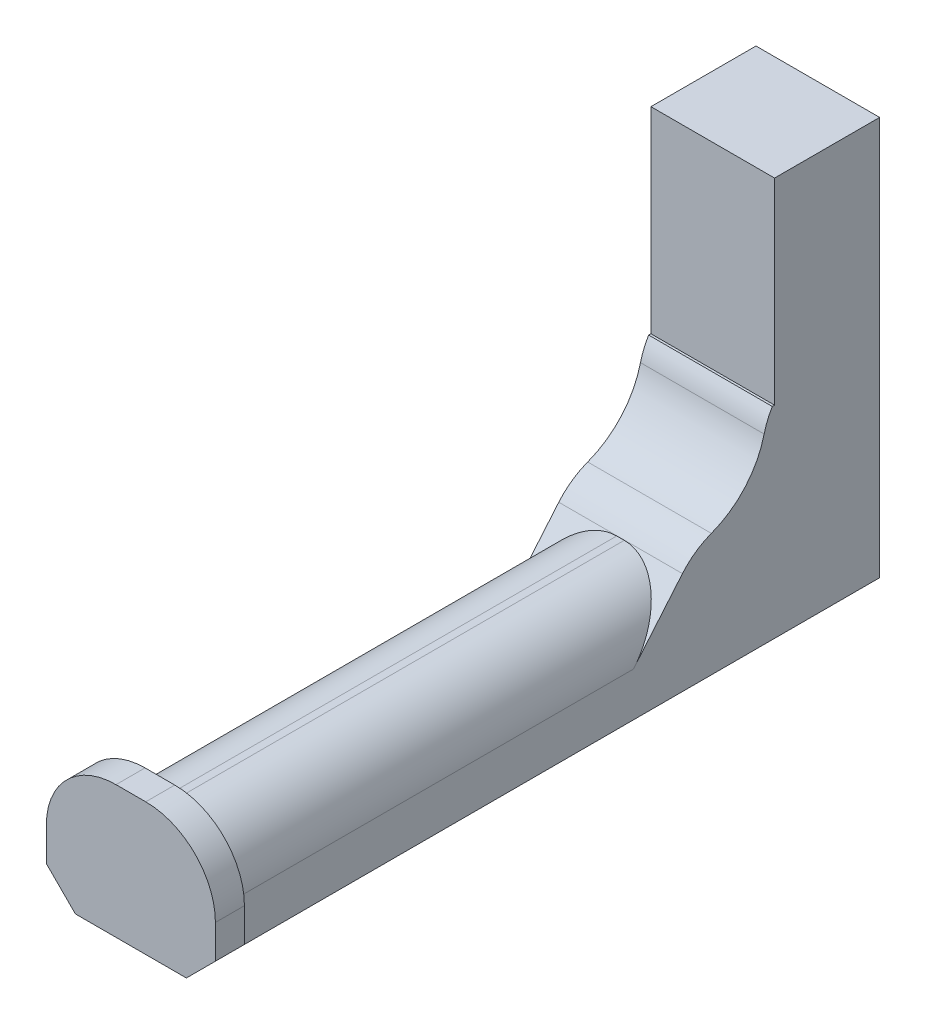
SolidWorks part; units mm, degrees
ref_plane "Front" through (0, 0, 0) normal (0, 0, 1) x (1, 0, 0)
ref_plane "Top" through (0, 0, 0) normal (0, 1, 0) x (1, 0, 0)
ref_plane "Right" through (0, 0, 0) normal (1, 0, 0) x (0, 0, -1)
sketch "Sketch1" plane through (0, 0, 0) normal (0, 0, 1) x (1, 0, 0)
  line L1 (-10.65, -35) -> (10.65, -35)
  line L2 (-10.65, -35) -> (-10.65, 35)
  line L3 (-10.65, 35) -> (10.65, 35)
  line L4 (10.65, -35) -> (10.65, 35)
  line L5 (-10.65, -35) -> (10.65, 35) construction
  line L6 (-10.65, 35) -> (10.65, -35) construction
  point P0 (0, 0)
extrude "Boss-Extrude1" add sketch "Sketch1" against normal blind 3
sketch "Sketch2" plane through (0, 0, -3) normal (0, 0, -1) x (-1, 0, 0)
  line L0 (10.65, -35) -> (-10.65, -35) construction
  line L1 (-10.65, 35) -> (-7.7, 35)
  line L2 (-10.65, 35) -> (-10.65, -35)
  line L3 (-10.65, -35) -> (-7.7, -35)
  line L4 (-7.7, 35) -> (-7.7, -35)
  line L6 (10.65, 35) -> (7.7, 35)
  line L7 (10.65, 35) -> (10.65, -35)
  line L8 (10.65, -35) -> (7.7, -35)
  line L9 (7.7, 35) -> (7.7, -35)
  dimension "D1" = 15.4
extrude "Boss-Extrude2" add sketch "Sketch2" along normal blind 15.1
sketch "Sketch3" plane through (0, 0, -3) normal (0, 0, -1) x (-1, 0, 0)
  line L0 (7.7, 35) -> (7.7, -35) construction
  line L1 (-7.7, 35) -> (7.7, 35)
  line L2 (-7.7, 35) -> (-7.7, 32)
  line L3 (-7.7, 32) -> (7.7, 32)
  line L4 (7.7, 35) -> (7.7, 32)
extrude "Boss-Extrude3" add sketch "Sketch3" along normal up to surface (15.1 mm away) up to face at (9.175, 0, -18.1)
sketch "Sketch4" plane through (0, 0, 0) normal (0, 0, 1) x (1, 0, 0)
  line L1 (-10.65, -16.0991) -> (10.65, -16.0991)
  line L2 (-10.65, -16.0991) -> (-10.65, -35)
  line L3 (-10.65, -35) -> (10.65, -35)
  line L4 (10.65, -16.0991) -> (10.65, -35)
  line L6 (-10.65, -35) -> (10.65, -35) construction
extrude "Boss-Extrude4" add sketch "Sketch4" along normal blind 95
sketch "Sketch6" plane through (0, 0, 95) normal (0, 0, 1) x (1, 0, 0)
  line L1 (-14.7909, -12.2147) -> (14.3271, -12.2147)
  line L2 (-14.7909, -12.2147) -> (-14.7909, -35)
  line L3 (-14.7909, -35) -> (14.3271, -35)
  line L4 (14.3271, -12.2147) -> (14.3271, -35)
  line L5 (-14.7909, -12.2147) -> (14.3271, -35) construction
  line L6 (-14.7909, -35) -> (14.3271, -12.2147) construction
  line L7 (-10.65, -35) -> (10.65, -35) construction
  point P0 (-0.2319, -23.6074)
extrude "Boss-Extrude5" add sketch "Sketch6" along normal blind 5
sketch "Sketch9" plane through (0, 0, 0) normal (0, 0, 1) x (1, 0, 0)
  line L0 (10.65, -16.0991) -> (10.65, 35) construction
  line L1 (-10.65, -16.0991) -> (10.65, -16.0991)
  line L2 (-10.65, -16.0991) -> (-10.65, 1.1229)
  line L3 (-10.65, 1.1229) -> (10.65, 1.1229)
  line L4 (10.65, -16.0991) -> (10.65, 1.1229)
extrude "Boss-Extrude6" add sketch "Sketch9" along normal blind 16
sketch "Sketch12" plane through (-10.65, 0, 0) normal (-1, 0, 0) x (0, 0, 1)
  circle A0 centre (16, 1.1229) radius 14.608
extrude "Cut-Extrude1" cut sketch "Sketch12" against normal through all
chamfer "Chamfer3" distance 3 angle 45 1 edges at (0, -13.4851, 16)
chamfer "Chamfer4" distance 1 angle 45 1 edges at (0, 1.1229, 1.392)
chamfer "Chamfer5" distance 5 angle 45 1 edges at (-14.7909, -35, 97.5)
chamfer "Chamfer6" distance 5 angle 45 1 edges at (14.3271, -35, 97.5)
fillet "Fillet4" radius 12 2 edges at (-14.7909, -12.2147, 97.5) (14.3271, -12.2147, 97.5)
fillet "Fillet5" radius 12 1 edges at (0, -13.2715, 13.5111)
fillet "Fillet6" radius 12 1 edges at (0, 0.0861, 1.4288)
fillet "Fillet7" radius 10 2 edges
